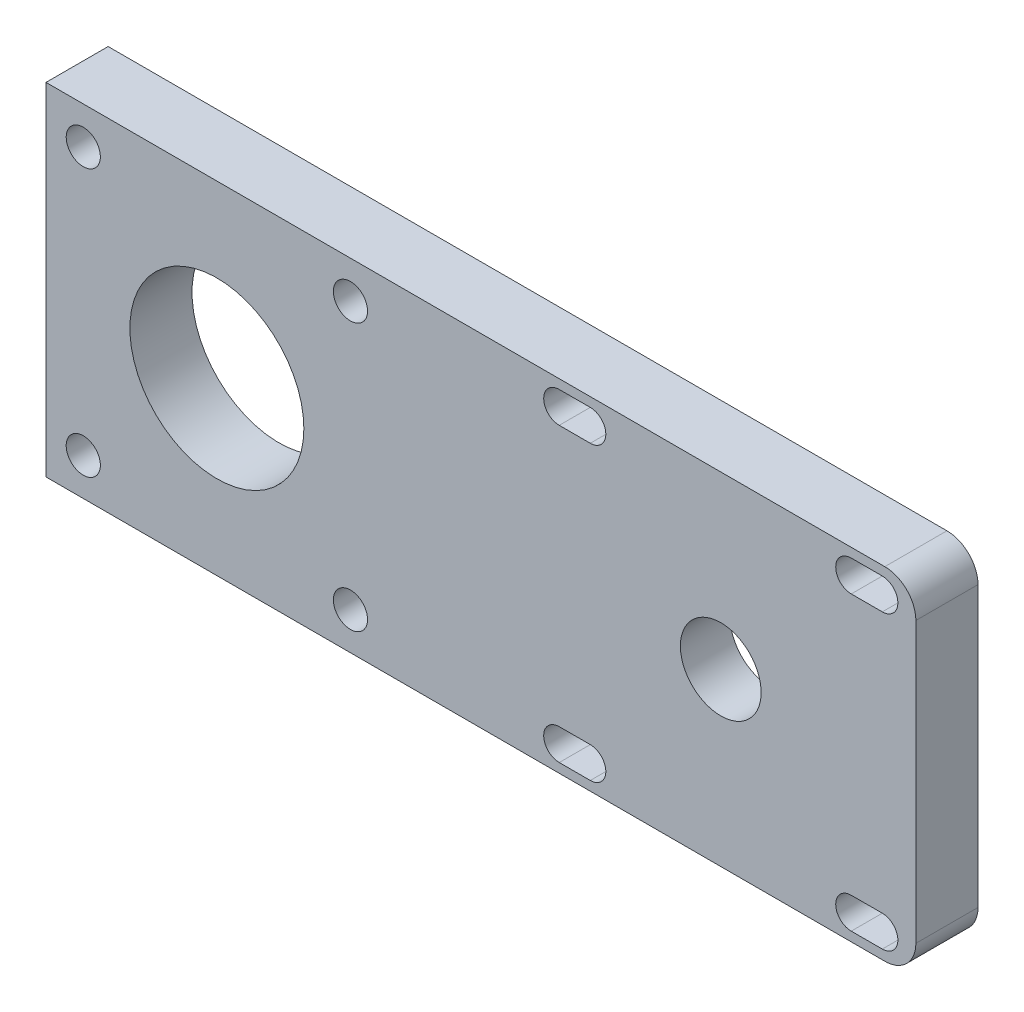
SolidWorks part; units mm, degrees
ref_plane "Piano frontale" through (0, 0, 0) normal (0, 0, 1) x (1, 0, 0)
ref_plane "Piano superiore" through (0, 0, 0) normal (0, 1, 0) x (1, 0, 0)
ref_plane "Piano destro" through (0, 0, 0) normal (1, 0, 0) x (0, 0, -1)
sketch "Schizzo1" plane through (0, 0, 0) normal (0, 0, 1) x (1, 0, 0)
  line L1 (0, 0) -> (140, 0)
  line L2 (0, 0) -> (0, 55)
  line L3 (0, 55) -> (140, 55)
  line L4 (140, 0) -> (140, 55)
  dimension "D1" = 55
  dimension "D2" = 140
extrude "Estrusione-Estrusione1" add sketch "Schizzo1" against normal blind 10
sketch "Schizzo2" plane through (0, 0, 0) normal (0, 0, 1) x (1, 0, 0)
  line L0 (0, 0) -> (0, 69.6041) construction
  line L1 (27.5, 0) -> (27.5, 69.6041) construction
  line L2 (0, 0) -> (60.1033, 0) construction
  line L3 (0, 0) -> (140, 0) construction
  line L4 (0, 27.5) -> (60.1033, 27.5) construction
  line L5 (6, 0) -> (6, 69.6041) construction
  line L6 (0, 6) -> (60.1033, 6) construction
  circle A0 centre (27.5, 27.5) radius 14
  circle A1 centre (6, 6) radius 2.75
  circle A2 centre (49, 6) radius 2.75
  circle A3 centre (49, 49) radius 2.75
  circle A4 centre (6, 49) radius 2.75
  dimension "D3" = 28
  dimension "D6" = 5.5
  dimension "D7" = 6
  dimension "D1" = 27.5
  dimension "D2" = 27.5
  dimension "D4" = 6
  dimension "D5" = 6
extrude "Taglio-Estrusione1" cut sketch "Schizzo2" against normal through all
fillet "Raccordo1" radius 5 2 edges at (140, 0, -5) (140, 55, -5)
sketch "Schizzo3" plane through (0, 0, -10) normal (0, 0, -1) x (-1, 0, 0)
  line L0 (-140, 25.5567) -> (-140, 74.1384) construction
  line L1 (-140, 5) -> (-140, 50) construction
  line L2 (-80.1, 25.5567) -> (-80.1, 74.1384) construction
  line L3 (-137.1, 25.5567) -> (-137.1, 74.1384) construction
  line L4 (-80.1, 27.5) -> (-137.1, 27.5) construction
  line L5 (-134.6, 51) -> (-129.6, 51) construction
  line L6 (-108.6, 27.5) -> (-108.6, 59.8878) construction
  line L8 (-132.1, 27.5) -> (-132.1, 64.4221) construction
  line L9 (-80.1, 51) -> (-137.1, 51) construction
  line L10 (-80.1, 4) -> (-137.1, 4) construction
  line L11 (-132.1, 27.5) -> (-132.1, 74.1384) construction
  line L13 (-108.6, 27.5) -> (-108.6, 74.1384) construction
  line L14 (-108.6, 55) -> (-145.2784, 55) construction
  line L15 (-135, 55) -> (0, 55) construction
  line L16 (-116.2061, 0) -> (-154.4249, 0) construction
  line L17 (0, 0) -> (-135, 0) construction
  line L18 (-134.6, 53.5) -> (-129.6, 53.5)
  line L19 (-134.6, 48.5) -> (-129.6, 48.5)
  line L20 (-82.6, 51) -> (-87.6, 51) construction
  line L21 (-82.6, 51) -> (-87.6, 51) construction
  line L22 (-82.6, 53.5) -> (-87.6, 53.5)
  line L23 (-82.6, 48.5) -> (-87.6, 48.5)
  line L24 (-134.6, 4) -> (-129.6, 4) construction
  line L25 (-134.6, 1.5) -> (-129.6, 1.5)
  line L26 (-134.6, 6.5) -> (-129.6, 6.5)
  line L27 (-82.6, 4) -> (-87.6, 4) construction
  line L28 (-82.6, 1.5) -> (-87.6, 1.5)
  line L29 (-82.6, 6.5) -> (-87.6, 6.5)
  arc A0 (-82.6, 53.5) -> (-82.6, 48.5) centre (-82.6, 51) cw
  arc A1 (-87.6, 48.5) -> (-87.6, 53.5) centre (-87.6, 51) cw
  arc A2 (-134.6, 1.5) -> (-134.6, 6.5) centre (-134.6, 4) cw
  arc A3 (-129.6, 6.5) -> (-129.6, 1.5) centre (-129.6, 4) cw
  arc A4 (-134.6, 53.5) -> (-134.6, 48.5) centre (-134.6, 51) ccw
  circle A5 centre (-108.6, 27.5) radius 6.5
  arc A6 (-129.6, 48.5) -> (-129.6, 53.5) centre (-129.6, 51) ccw
  arc A7 (-82.6, 1.5) -> (-82.6, 6.5) centre (-82.6, 4) ccw
  arc A8 (-87.6, 6.5) -> (-87.6, 1.5) centre (-87.6, 4) ccw
  point P20 (-85.1, 51)
  point P33 (-132.1, 4)
  point P45 (-132.1, 51)
  point P58 (-85.1, 4)
  dimension "D10" = 5
  dimension "D11" = 13
  dimension "D12" = 5
  dimension "D3" = 23.5
  dimension "D1" = 59.9
  dimension "D2" = 57
  dimension "D5" = 23.5
  dimension "D6" = 23.5
extrude "Taglio-Estrusione2" cut sketch "Schizzo3" against normal through all
sketch "Schizzo4" plane through (0, 0, -10) normal (0, 0, -1) x (-1, 0, 0)
  line L1 (-88.6, 9) -> (-128.6, 9)
  line L2 (-83.6, 14) -> (-83.6, 41)
  line L3 (-88.6, 46) -> (-128.6, 46)
  line L4 (-133.6, 14) -> (-133.6, 41)
  line L5 (-83.6, 9) -> (-133.6, 46) construction
  line L6 (-83.6, 46) -> (-133.6, 9) construction
  arc A0 (-88.6, 46) -> (-83.6, 41) centre (-88.6, 41) cw
  arc A1 (-83.6, 14) -> (-88.6, 9) centre (-88.6, 14) cw
  arc A2 (-128.6, 9) -> (-133.6, 14) centre (-128.6, 14) cw
  arc A3 (-133.6, 41) -> (-128.6, 46) centre (-128.6, 41) cw
  point P0 (-108.6, 27.5)
  dimension "D1" = 50
  dimension "D3" = 5
  dimension "D2" = 37
extrude "Taglio-Estrusione3" cut sketch "Schizzo4" against normal blind 2
